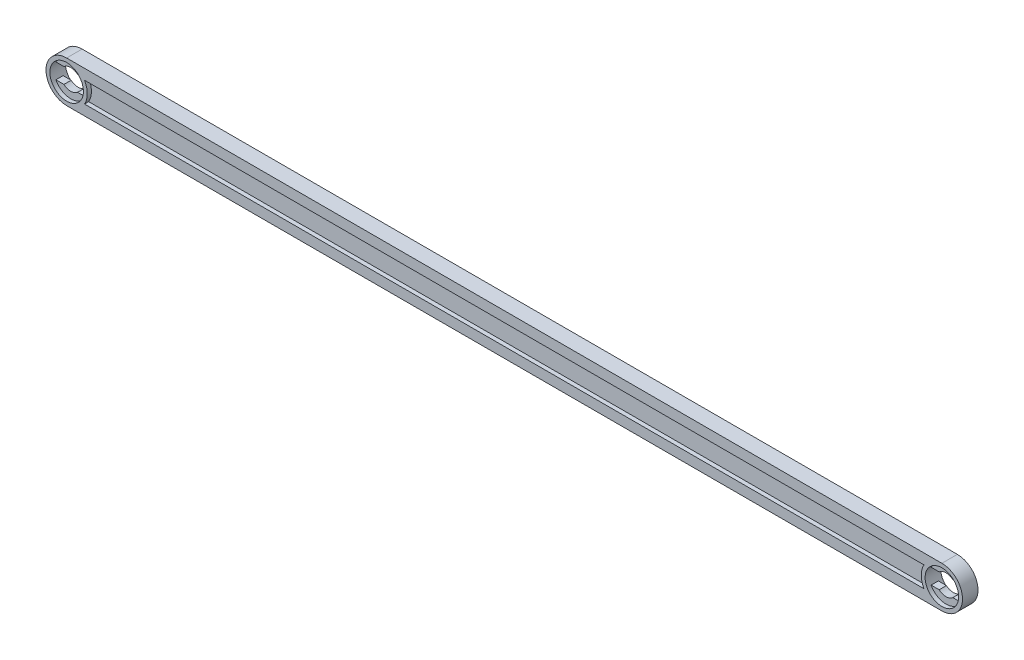
SolidWorks part; units mm, degrees
ref_plane "前视基准面" through (0, 0, 0) normal (0, 0, 1) x (1, 0, 0)
ref_plane "上视基准面" through (0, 0, 0) normal (0, 1, 0) x (1, 0, 0)
ref_plane "右视基准面" through (0, 0, 0) normal (1, 0, 0) x (0, 0, -1)
sketch "草图1" plane through (0, 0, 0) normal (0, 0, 1) x (1, 0, 0)
  line L1 (0, 4) -> (169.6, 4)
  line L3 (0, -4) -> (169.6, -4)
  arc A0 (0, 4) -> (0, -4) centre (0, 0) ccw
  arc A1 (169.6, -4) -> (169.6, 4) centre (169.6, 0) ccw
  dimension "D1" = 169.6
  dimension "D2" = 4
  dimension "D4" = 4
  dimension "D3" = 169.6
extrude "凸台-拉伸1" add sketch "草图1" against normal blind 3
sketch "草图2" plane through (0, 0, 0) normal (0, 0, 1) x (1, 0, 0)
  line L0 (1.3229, -1.5) -> (2.8831, -1.5)
  line L1 (-2.8831, -1.5) -> (-1.3229, -1.5)
  line L2 (1.3229, 1.5) -> (2.8831, 1.5)
  line L3 (-2.8831, 1.5) -> (-1.3229, 1.5)
  arc A0 (1.3229, 1.5) -> (-1.3229, 1.5) centre (0, 0) ccw
  arc A1 (-2.8831, 1.5) -> (-2.8831, -1.5) centre (0, 0) ccw
  arc A3 (2.8831, -1.5) -> (2.8831, 1.5) centre (0, 0) ccw
  arc A4 (-1.3229, -1.5) -> (1.3229, -1.5) centre (0, 0) ccw
extrude "切除-拉伸1" cut sketch "草图2" against normal up to next
sketch "草图3" plane through (0, 0, 0) normal (0, 0, 1) x (1, 0, 0)
  circle A1 centre (0, 0) radius 3.25
extrude "切除-拉伸2" cut sketch "草图3" against normal blind 0.8
extrude "切除-拉伸3" cut sketch "草图3<2>" along normal blind 0.8 from offset 3 offset against normal yes
sketch "草图3<2>" plane through (0, 0, 0) normal (0, 0, 1) x (1, 0, 0) same geometry as "草图3"
pattern_linear "阵列(线性)1" count 2 spacing 169.6 along (1, 0, 0) of "切除-拉伸1", "切除-拉伸2", "切除-拉伸3"
sketch "草图4" plane through (0, 0, 0) normal (0, 0, 1) x (1, 0, 0)
  line L0 (0, 0) -> (0, 2) construction
  line L1 (0, 0) -> (0, -2) construction
  line L2 (0, 2) -> (3.4641, 2) construction
  line L3 (0, -2) -> (3.4641, -2) construction
  line L4 (169.6, 0) -> (169.6, 2) construction
  line L5 (169.6, 2) -> (166.1359, 2) construction
  line L6 (169.6, 0) -> (169.6, -2) construction
  line L7 (169.6, -2) -> (166.1359, -2) construction
  line L8 (3.4641, 2) -> (166.1359, 2)
  line L9 (3.4641, -2) -> (166.1359, -2)
  arc A0 (1.3229, 1.5) -> (-1.3229, 1.5) centre (0, 0) ccw construction
  arc A1 (-1.3229, -1.5) -> (1.3229, -1.5) centre (0, 0) ccw construction
  arc A2 (3.4641, -2) -> (3.4641, 2) centre (0, 0) ccw
  arc A3 (166.1359, 2) -> (166.1359, -2) centre (169.6, 0) ccw
  arc A4 (170.9229, 1.5) -> (168.2771, 1.5) centre (169.6, 0) ccw construction
  arc A5 (168.2771, -1.5) -> (170.9229, -1.5) centre (169.6, 0) ccw construction
extrude "切除-拉伸4" cut sketch "草图4" against normal blind 0.8
sketch "草图5" plane through (0, 0, -3) normal (0, 0, -1) x (-1, 0, 0)
  line L0 (-165.6, -2) -> (-165.6, 2)
  line L1 (-4, -2) -> (-4, 2)
  line L2 (-165.6, 2) -> (-4, 2)
  line L3 (-165.6, 0) -> (-4, 0) construction
  line L4 (-165.6, -2) -> (-4, -2)
  circle A0 centre (-169.6, 0) radius 4 construction
  circle A1 centre (0, 0) radius 4 construction
  dimension "D1" = 2
  dimension "D2" = 2
extrude "切除-拉伸5" cut sketch "草图5" against normal blind 0.8
